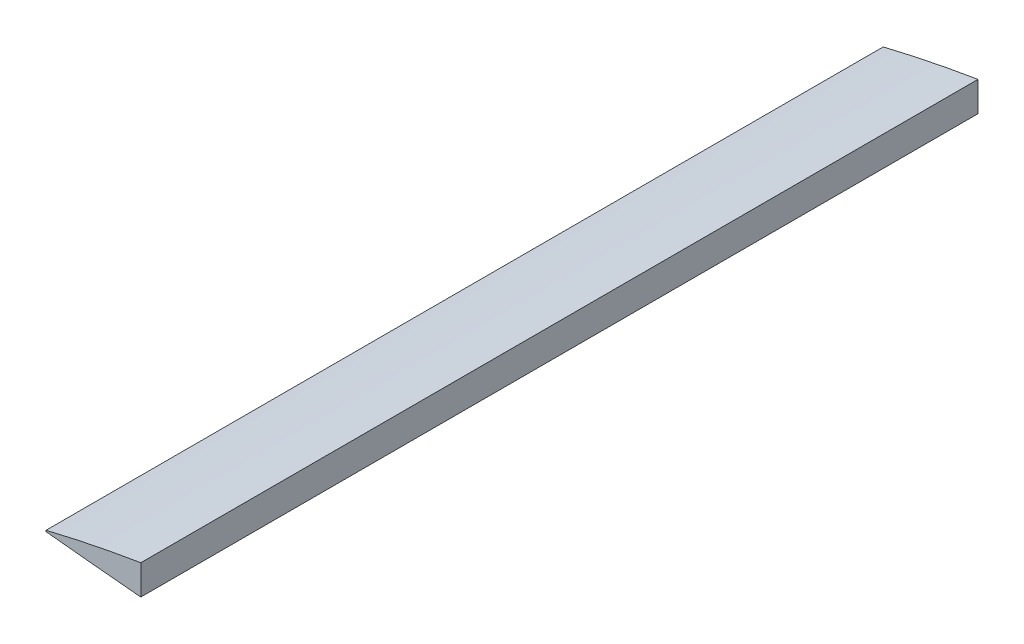
SolidWorks part; units mm, degrees
ref_plane "Front Plane" through (0, 0, 0) normal (0, 0, 1) x (1, 0, 0)
ref_plane "Top Plane" through (0, 0, 0) normal (0, 1, 0) x (1, 0, 0)
ref_plane "Right Plane" through (0, 0, 0) normal (1, 0, 0) x (0, 0, -1)
sketch "Sketch1" plane through (0, 0, 0) normal (0, 0, 1) x (1, 0, 0)
  line L0 (-197.267, 14.5456) -> (-197.267, -7.2089)
  line L1 (-266.577, 0.4257) -> (-266.577, -0.4189)
  spline S0 degree 3 poles (-197.267, 14.5456) (-199.2913, 14.2098) (-204.2167, 13.3929) (-211.8679, 12.0299) (-220.0467, 10.5109) (-227.685, 9.0242) (-234.7376, 7.5953) (-241.1628, 6.245) (-246.9227, 4.9942) (-251.9835, 3.8631) (-256.316, 2.8703) (-259.895, 2.0327) (-262.7001, 1.365) (-264.7152, 0.8792) (-265.9195, 0.5864) (-266.4509, 0.4566) (-266.577, 0.4257) knots 0 0 0 0 0.087007 0.211705 0.329527 0.439741 0.541661 0.634652 0.718135 0.791585 0.85454 0.906603 0.947445 0.976805 0.994497 1 1 1 1
  spline S1 degree 3 poles (-197.267, -7.2089) (-199.0197, -7.05) (-203.6784, -6.6277) (-211.0841, -5.9396) (-219.3093, -5.1648) (-227.0092, -4.427) (-234.1351, -3.7336) (-240.6411, -3.0907) (-246.4855, -2.5047) (-251.6304, -1.981) (-256.0423, -1.5274) (-259.6922, -1.1436) (-262.5569, -0.8499) (-264.6155, -0.6129) (-265.8584, -0.5128) (-266.419, -0.4184) (-266.5677, -0.4189) (-266.577, -0.4189) knots 0 0 0 0 0.075811 0.201508 0.320388 0.431695 0.534719 0.628797 0.713321 0.78774 0.851567 0.90438 0.945827 0.975633 0.993597 0.999599 1 1 1 1
extrude "Boss-Extrude1" add sketch "Sketch1" against normal blind 612
ref_plane "Plane1" through (0, 0, -96.9) normal (0, 0, 1) x (1, 0, 0)
sketch "Sketch2" plane through (0, 0, -96.9) normal (0, 0, 1) x (1, 0, 0)
  line L0 (-220.432, -7.777) -> (-199.432, -7.777)
  line L1 (-199.432, -7.777) -> (-199.432, 3.723)
  line L2 (-199.432, 3.723) -> (-220.432, 3.723)
  line L3 (-220.432, 3.723) -> (-220.432, -7.777)
extrude "Cut-Extrude1" cut sketch "Sketch2" along normal blind 13
